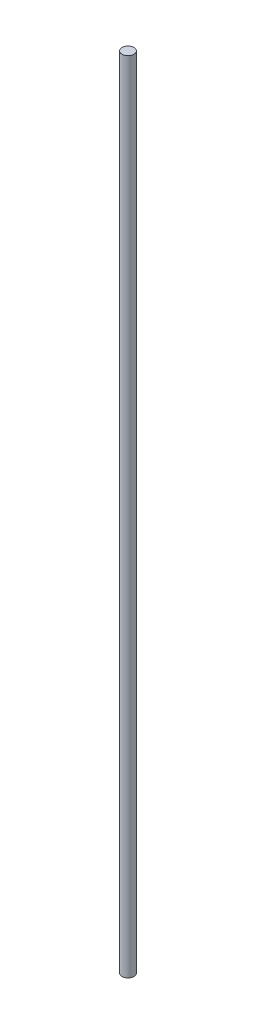
SolidWorks part; units mm, degrees
ref_plane "Plan de face" through (0, 0, 0) normal (0, 0, 1) x (1, 0, 0)
ref_plane "Plan de dessus" through (0, 0, 0) normal (0, 1, 0) x (1, 0, 0)
ref_plane "Plan de droite" through (0, 0, 0) normal (1, 0, 0) x (0, 0, -1)
sketch "Esquisse1" plane through (0, 0, 0) normal (0, 1, 0) x (1, 0, 0)
  circle A0 centre (0, 0) radius 2.5
  dimension "D1" = 5
extrude "Boss.-Extru.1" add sketch "Esquisse1" along normal up to surface (335.7 mm away)
